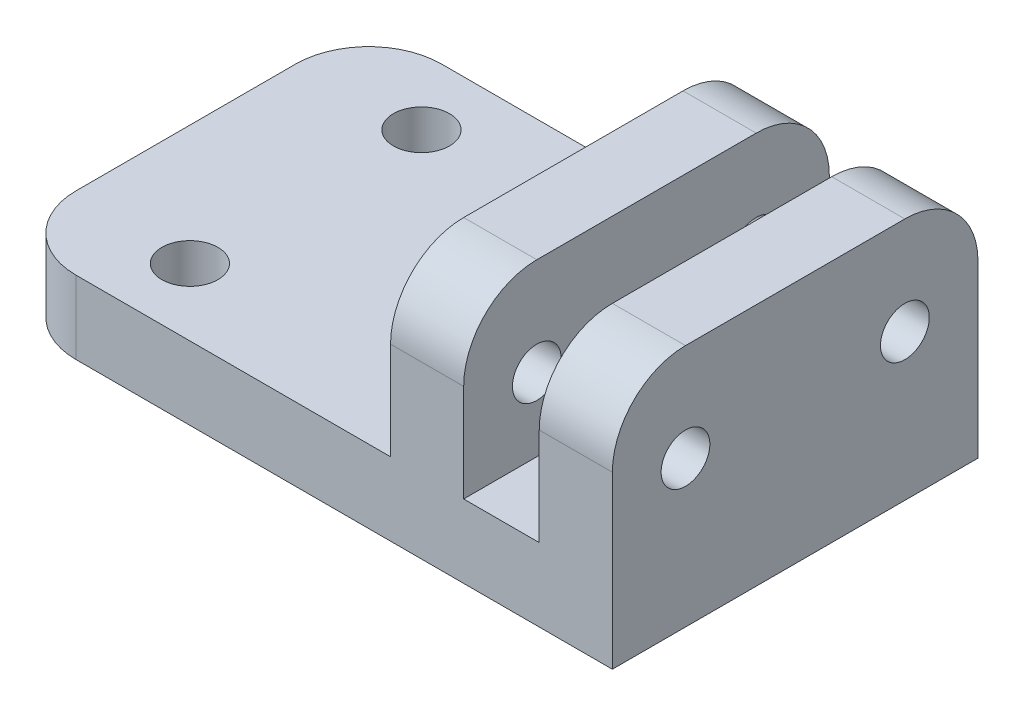
SolidWorks part; units mm, degrees
ref_plane "Plan de face" through (0, 0, 0) normal (0, 0, 1) x (1, 0, 0)
ref_plane "Plan de dessus" through (0, 0, 0) normal (0, 1, 0) x (1, 0, 0)
ref_plane "Plan de droite" through (0, 0, 0) normal (1, 0, 0) x (0, 0, -1)
sketch "Sketch1" plane through (0, 0, 0) normal (0, 1, 0) x (1, 0, 0)
  line L0 (4.9175, 12.25) -> (4.9175, 2.75) construction
  line L1 (0, 0) -> (25, 0)
  line L2 (0, 0) -> (0, 15)
  line L3 (0, 15) -> (25, 15)
  line L4 (25, 0) -> (25, 15)
  line L6 (15.9, 15) -> (18.9, 15)
  line L7 (15.9, 15) -> (15.9, 0)
  line L8 (15.9, 0) -> (18.9, 0)
  line L9 (18.9, 15) -> (18.9, 0)
  line L10 (25, 15) -> (22, 15)
  line L11 (25, 15) -> (25, 0)
  line L12 (25, 0) -> (22, 0)
  line L13 (22, 15) -> (22, 0)
  circle A0 centre (4.9175, 12.25) radius 1.15
  circle A1 centre (4.9175, 2.75) radius 1.15
  point P9 (4.9175, 7.5)
  point P10 (0, 7.5)
  dimension "D3" = 2.3
  dimension "D4" = 2.3
  dimension "D6" = 3.1
  dimension "D7" = 3
  dimension "D8" = 3
  dimension "D1" = 15
  dimension "D2" = 25
  dimension "D5" = 9.5
extrude "Boss-Extrude1" add sketch "Sketch1" along normal blind 3 contours L7 L3 L2 L1 A0 A1 | L13 L3 L9 L1 | L3 L13 L1 L4 | L9 L3 L7 L1 region at (8.0595, 0, -7.5) region at (17.4, 0, -7.5) region at (20.45, 0, -7.5) region at (23.5, 0, -7.5)
fillet "Fillet1" radius 3 4 edges at (0, 1.5, -15) (25, 1.5, -15) (25, 1.5, 0) (0, 1.5, 0)
extrude "Boss-Extrude2" add sketch "Sketch1<3>" along normal blind 10 contours L9 L3 L7 L1 | L3 L13 L1 L4 region at (17.4, 0, -7.5) region at (23.5, 0, -7.5)
sketch "Sketch1<3>" plane through (0, 0, 0) normal (0, 1, 0) x (1, 0, 0) same geometry as "Sketch1"
sketch "Sketch2" plane through (15.9, 0, 0) normal (-1, 0, 0) x (0, 0, 1)
  line L0 (-15, 10) -> (-15, 3) construction
  line L1 (0, 3) -> (-15, 3) construction
  circle A0 centre (-12, 6) radius 1
  circle A1 centre (-3, 6) radius 1
  dimension "D1" = 2
  dimension "D2" = 2
  dimension "D3" = 9
  dimension "D4" = 3
  dimension "D5" = 3
extrude "Cut-Extrude1" cut sketch "Sketch2" against normal through all both and the other way through all
fillet "Fillet2" radius 3 4 edges at (23.5, 10, 0) (17.4, 10, 0) (23.5, 10, -15) (17.4, 10, -15)
